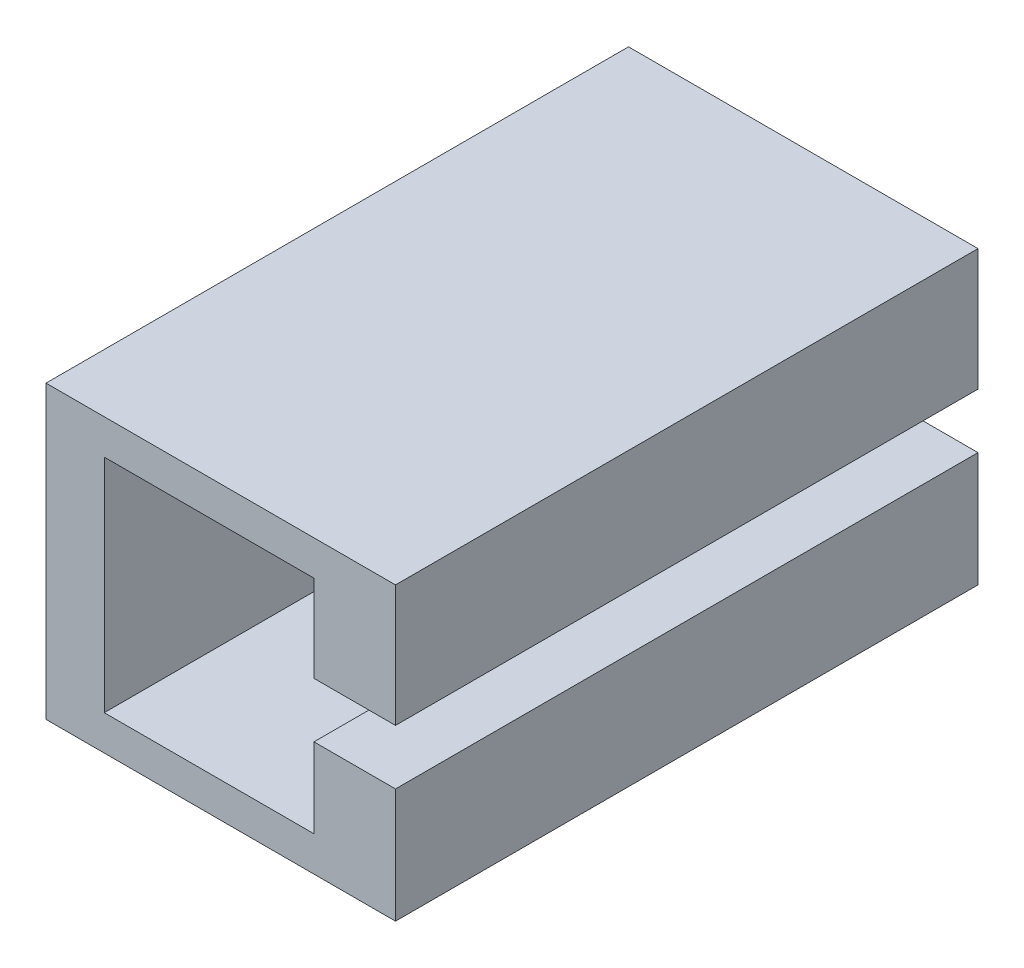
SolidWorks part; units mm, degrees
ref_plane "Front Plane" through (0, 0, 0) normal (0, 0, 1) x (1, 0, 0)
ref_plane "Top Plane" through (0, 0, 0) normal (0, 1, 0) x (1, 0, 0)
ref_plane "Right Plane" through (0, 0, 0) normal (1, 0, 0) x (0, 0, -1)
sketch "Sketch1" plane through (0, 0, 0) normal (0, 0, 1) x (1, 0, 0)
  line L2 (0, 0) -> (0, 25)
  line L11 (0, 25) -> (30, 25)
  line L17 (30, 0) -> (0, 0)
  line L19 (5, 22) -> (5, 3)
  line L21 (30, 25) -> (30, 14.5534)
  line L22 (30, 14.5534) -> (23, 14.5534)
  line L23 (23, 14.5534) -> (23, 22)
  line L24 (23, 22) -> (5, 22)
  line L25 (5, 3) -> (23, 3)
  line L26 (23, 3) -> (23, 9.8332)
  line L27 (23, 9.8332) -> (30, 9.8332)
  line L28 (30, 9.8332) -> (30, 0)
  dimension "D1" = 25
  dimension "D2" = 30
  dimension "D3" = 30
  dimension "D4" = 18
  dimension "D6" = 19
extrude "Boss-Extrude1" add sketch "Sketch1" along normal blind 50
sketch "Sketch3" plane through (0, 0, 0) normal (-1, 0, 0) x (0, 0, 1)
  line L0 (4.9195, 16.0567) -> (21.9195, 16.0567)
  line L1 (21.9195, 16.0567) -> (21.9195, 24.0567)
  line L2 (21.9195, 24.0567) -> (27.9195, 24.0567)
  line L3 (27.9195, 24.0567) -> (27.9195, 16.0567)
  line L4 (27.9195, 16.0567) -> (42.9195, 16.0567)
  line L5 (42.9195, 16.0567) -> (42.9195, 9.0567)
  line L6 (42.9195, 9.0567) -> (27.9195, 9.0567)
  line L7 (27.9195, 9.0567) -> (27.9195, 1.0567)
  line L8 (27.9195, 1.0567) -> (21.9195, 1.0567)
  line L9 (21.9195, 1.0567) -> (21.9195, 9.0567)
  line L10 (21.9195, 9.0567) -> (4.9195, 9.0567)
  line L13 (4.9195, 16.0567) -> (4.9195, 9.0567)
  circle A0 centre (40.25, 12.5203) radius 0.55
  circle A1 centre (8.9802, 12.5203) radius 0.55
  point P16 (9.1578, 12.1756)
  point P17 (0, 0)
  point P18 (9.0151, 12.3296)
  point P19 (8.9802, 12.5203)
  point P20 (0, 0)
  point P21 (0, 0)
  dimension "D12" = 1.1
  dimension "D13" = 1.1
  dimension "D1" = 7
  dimension "D2" = 8
  dimension "D3" = 8
  dimension "D4" = 7
  dimension "D5" = 8
  dimension "D6" = 6
  dimension "D7" = 17
  dimension "D8" = 17
  dimension "D9" = 15
  dimension "D10" = 15
  dimension "D11" = 6
extrude "Cut-Extrude1" cut sketch "Sketch3" against normal blind 3
